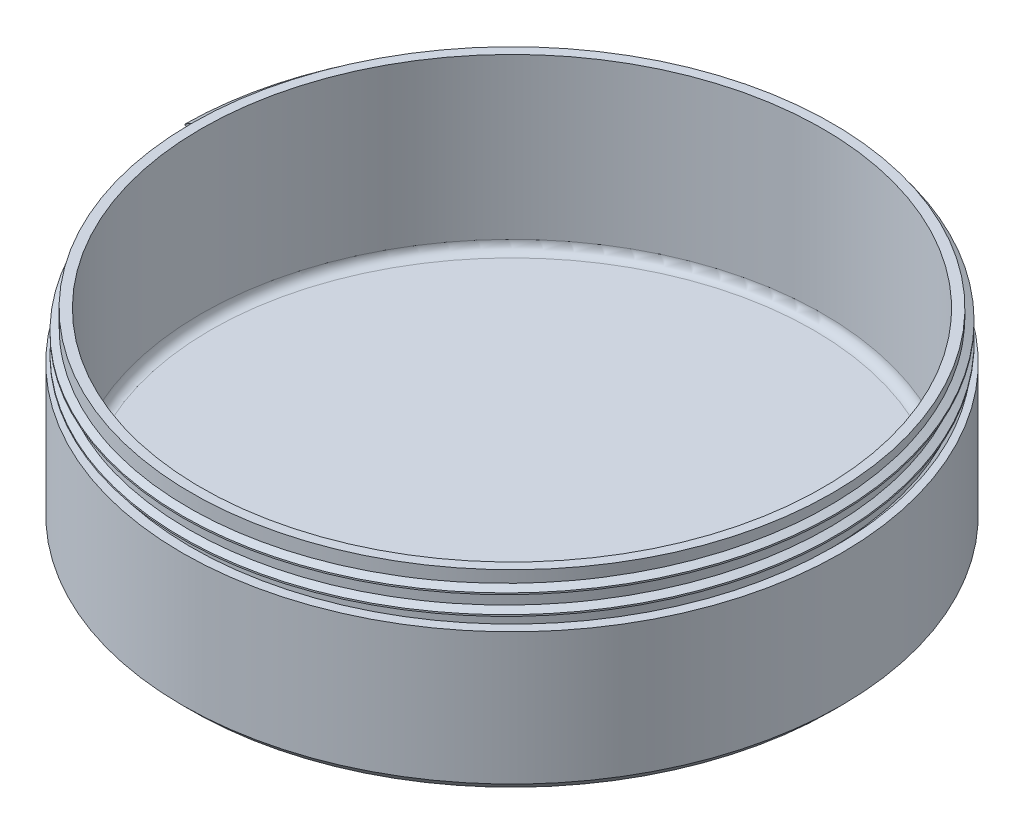
SolidWorks part; units mm, degrees
ref_plane "Спереди" through (0, 0, 0) normal (0, 0, 1) x (1, 0, 0)
ref_plane "Сверху" through (0, 0, 0) normal (0, 1, 0) x (1, 0, 0)
ref_plane "Справа" through (0, 0, 0) normal (1, 0, 0) x (0, 0, -1)
other "Configuration Table"
sketch "Эскиз1" plane through (0, 0, 0) normal (0, 0, 1) x (1, 0, 0)
  line L0 (0, 0) -> (-35, 0)
  line L1 (-35, 0) -> (-35, 15)
  line L4 (-33, 2) -> (0, 2)
  line L5 (0, 2) -> (0, 0)
  line L6 (-35, 15) -> (-34, 15)
  line L7 (-34, 15) -> (-34, 20)
  line L8 (-34, 20) -> (-33, 20)
  line L10 (-33, 20) -> (-33, 2)
  dimension "D1" = 35
  dimension "D2" = 1
  dimension "D3" = 2
  dimension "D4" = 15
  dimension "D5" = 1
  dimension "D6" = 5
revolve "Повернуть1" add sketch "Эскиз1" angle 360 about L5
chamfer "Фаска1" distance 1 angle 45 1 edges at (-35, 0, 0)
thread "Резьба1" pitch 1.27 method extrude profile "Профиль резьбы1" start angle 0, offset 0, length 5, pitch 2, diameter 68
ref_plane "Плоскость1" through (-34, 20, 0) normal (0, 0, 1) x (-1, 0, 0)
sketch "Профиль резьбы1" plane through (-34, 20, 0) normal (0, 0, 1) x (-1, 0, 0)
  line L0 (0, 0) -> (0, 1.27) construction
  line L1 (0, 0) -> (0.6874, 0.3969)
  line L2 (0.6874, 0.3969) -> (0.6874, 0.5556)
  line L3 (0.6874, 0.5556) -> (0, 0.9525)
  line L4 (0.6874, 0.4762) -> (0, 0.4762) construction
  line L11 (0, 0) -> (0, 0.9525)
  point P2 (0, 0)
  dimension "Pitch" = 1.27
  dimension "Profile_Angle" = 60
  dimension "Profile_Land" = 0.1588
  dimension "Profile_Height" = 0.6874
fillet "Скругление1" radius 1 1 edges at (-33, 2, 0)
equation "\"m\"=3"
